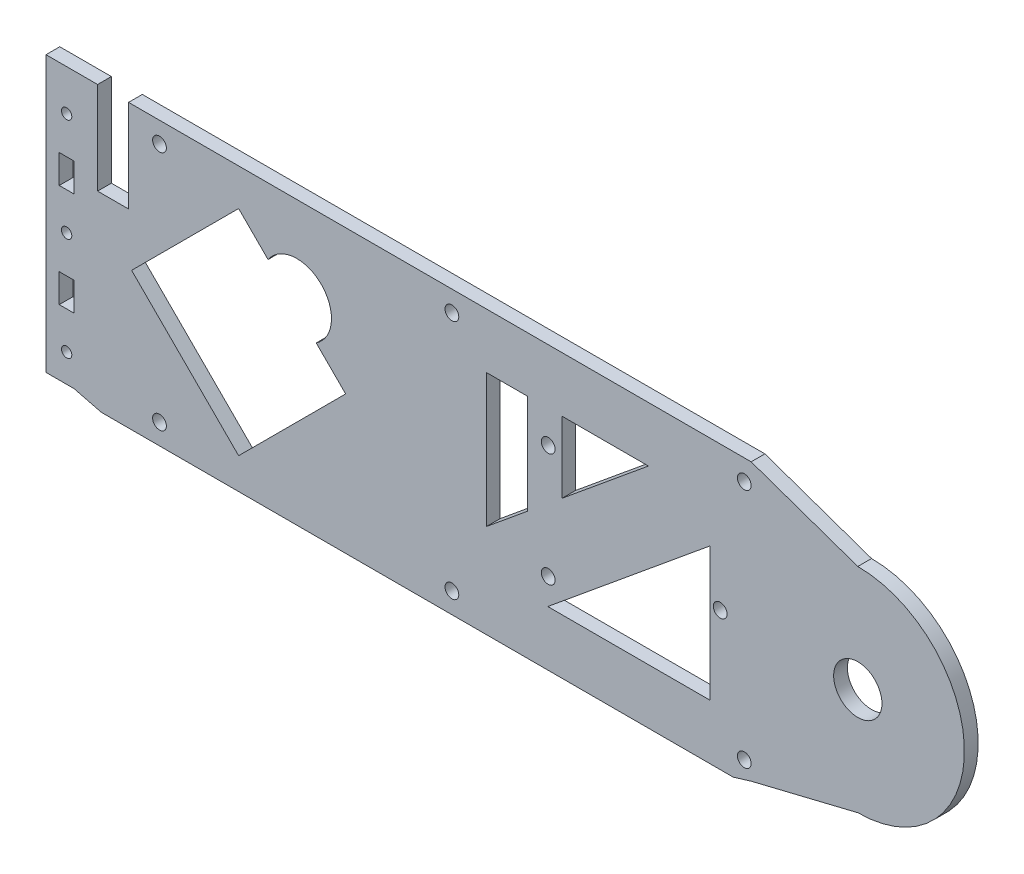
SolidWorks part; units mm, degrees
ref_plane "前视基准面" through (0, 0, 0) normal (0, 0, 1) x (1, 0, 0)
ref_plane "上视基准面" through (0, 0, 0) normal (0, 1, 0) x (1, 0, 0)
ref_plane "右视基准面" through (0, 0, 0) normal (1, 0, 0) x (0, 0, -1)
sketch "草图1" plane through (0, 0, 0) normal (0, 0, 1) x (1, 0, 0)
  line L0 (0.5429, 31.3543) -> (0.5429, 28.3543)
  line L1 (0.5429, 18.8543) -> (0.5429, 10.8543) construction
  line L2 (-1.6071, 10.7043) -> (2.6929, 10.7043)
  line L3 (-1.6071, 10.7043) -> (-1.6071, 19.0043)
  line L4 (-1.6071, 19.0043) -> (2.6929, 19.0043)
  line L5 (2.6929, 10.7043) -> (2.6929, 19.0043)
  line L6 (-1.6071, 10.7043) -> (2.6929, 19.0043) construction
  line L7 (-1.6071, 19.0043) -> (2.6929, 10.7043) construction
  line L8 (2.6929, -19.2957) -> (2.6929, -10.9957)
  line L9 (-1.6071, -19.2957) -> (2.6929, -19.2957)
  line L10 (-1.6071, -19.2957) -> (-1.6071, -10.9957)
  line L11 (-1.6071, -10.9957) -> (2.6929, -10.9957)
  line L12 (0.5429, -0.1457) -> (-6.4571, -0.1457) construction
  line L18 (50.5429, -0.1457) -> (96.7433, -0.1457) construction
  line L19 (50.5429, -0.1457) -> (230.5429, -0.1457) construction
  line L20 (199.5429, -0.1457) -> (199.5429, 38.0043) construction
  line L42 (230.5429, -31.1457) -> (199.5561, -38.7059)
  line L43 (199.5561, -38.7059) -> (174.5429, -46.2957)
  line L44 (174.5429, -46.2957) -> (34.5429, -46.2957)
  line L45 (34.5429, -46.2957) -> (2.6929, -38.2957)
  line L47 (2.6929, -38.2957) -> (-5.4571, -38.2957)
  line L48 (-5.4571, -38.2957) -> (-5.4571, 41.7043)
  line L49 (-5.4571, 41.7043) -> (9.5429, 41.7043)
  line L54 (199.5429, 41.7043) -> (230.5429, 30.8543)
  line L55 (9.5429, 41.7043) -> (9.5429, 14.8543)
  line L57 (9.5429, 14.8543) -> (18.5429, 14.8543)
  line L59 (-5.4571, 41.7043) -> (261.5429, 41.7043) construction
  line L60 (18.5429, 41.7043) -> (199.5429, 41.7043)
  line L61 (18.5429, 41.7043) -> (18.5429, 14.8543)
  line L62 (50.5429, 13.8543) -> (59.0992, 22.4106) construction
  line L63 (64.5429, -0.1457) -> (73.0992, 8.4106) construction
  line L64 (59.0992, 22.4106) -> (50.5429, 30.967)
  line L65 (19.4302, -0.1457) -> (50.5429, 30.967)
  line L66 (19.4302, -0.1457) -> (50.5429, -31.2584)
  line L67 (50.5429, -31.2584) -> (81.6556, -0.1457)
  line L68 (50.5429, 30.967) -> (81.6556, -0.1457) construction
  line L69 (19.4302, -0.1457) -> (81.6556, -0.1457) construction
  line L70 (50.5429, -31.2584) -> (50.5429, 30.967) construction
  line L71 (73.0992, 8.4106) -> (81.6556, -0.1457)
  line L72 (0.5429, -0.1457) -> (50.5429, -0.1457) construction
  circle A0 centre (0.5429, 29.8543) radius 1.5
  circle A1 centre (0.5429, -0.1457) radius 1.5
  circle A2 centre (0.5429, -30.1457) radius 1.5
  circle A15 centre (230.5429, -0.1457) radius 7.02
  circle A16 centre (230.5429, -0.1457) radius 31 construction
  arc A17 (230.5429, -31.1457) -> (230.5429, 30.8543) centre (230.5429, -0.1457) ccw
  circle A18 centre (50.5429, -0.1457) radius 34 construction
  arc A19 (59.0992, 22.4106) -> (73.0992, 8.4106) centre (67.4545, 16.7659) cw
  point P6 (0.5429, 14.8543)
  point P25 (50.5429, -0.1457)
  dimension "D3" = 44
  dimension "D4" = 44
  dimension "D10" = 3
  dimension "D13" = 14.04
  dimension "D1" = 8.3
  dimension "D2" = 4.3
  dimension "D5" = 50
  dimension "D7" = 15
  dimension "D8" = 60
  dimension "D9" = 30
  dimension "D14" = 180
extrude "凸台-拉伸1" add sketch "草图1" along normal blind 4 contours A2 A1 A0 L5 L2 L3 L4 L10 L11 L8 L9 region at (128.4702, -2.0106, 0)
sketch "草图3" plane through (0, 0, 4) normal (0, 0, 1) x (1, 0, 0)
  line L0 (18.5429, 41.7043) -> (199.5429, 41.7043) construction
  line L1 (18.5429, 41.7043) -> (18.5429, 14.8543) construction
  line L3 (112.5429, -34.2957) -> (197.5429, 35.7043) construction
  line L4 (197.5429, 35.7043) -> (197.5429, -34.2957) construction
  line L5 (197.5429, -34.2957) -> (112.5429, -34.2957) construction
  line L6 (187.5429, -24.2957) -> (140.4162, -24.2957)
  line L7 (140.4162, -24.2957) -> (187.5429, 14.5145)
  line L8 (187.5429, 14.5145) -> (187.5429, -24.2957)
  line L9 (112.5429, -34.2957) -> (112.5429, 35.7043) construction
  line L10 (112.5429, 35.7043) -> (197.5429, 35.7043) construction
  line L11 (122.5429, 25.7043) -> (169.6695, 25.7043)
  line L12 (122.5429, -13.1059) -> (169.6695, 25.7043)
  line L13 (122.5429, -13.1059) -> (122.5429, 25.7043)
  circle A0 centre (27.5429, 35.7043) radius 2
  circle A1 centre (112.5429, 35.7043) radius 2
  circle A2 centre (197.5429, 35.7043) radius 2
  circle A3 centre (112.5429, -34.2957) radius 2
  circle A4 centre (197.5429, -34.2957) radius 2
  circle A5 centre (27.5429, -34.2957) radius 2
  dimension "D1" = 6
  dimension "D2" = 9
  dimension "D5" = 10
  dimension "D6" = 10
  dimension "D3" = 3
  dimension "D4" = 2
extrude "切除-拉伸2" cut sketch "草图3" against normal blind 4
sketch "草图4" plane through (0, 0, 4) normal (0, 0, 1) x (1, 0, 0)
  line L0 (169.6695, 25.7043) -> (122.5429, 25.7043) construction
  line L1 (134.5429, -7.8425) -> (144.5429, -7.8425)
  line L2 (134.5429, -7.8425) -> (134.5429, 39.251)
  line L3 (134.5429, 39.251) -> (144.5429, 39.251)
  line L4 (144.5429, -7.8425) -> (144.5429, 39.251)
  line L5 (134.5429, -7.8425) -> (144.5429, 39.251) construction
  line L6 (134.5429, 39.251) -> (144.5429, -7.8425) construction
  point P0 (139.5429, 15.7043)
  dimension "D1" = 17
  dimension "D2" = 10
  dimension "D3" = 10
extrude "凸台-拉伸2" add sketch "草图4" against normal blind 4
sketch "草图7" plane through (0, 0, 4) normal (0, 0, 1) x (1, 0, 0)
  line L0 (10.6554, -40.2957) -> (194.3167, -40.2957)
  line L4 (34.5429, -46.2957) -> (2.6929, -38.2957) construction
  line L5 (199.5561, -38.7059) -> (174.5429, -46.2957) construction
  line L7 (10.6554, -40.2957) -> (10.6554, -65.8741)
  line L8 (10.6554, -65.8741) -> (206.1971, -67.6189)
  line L9 (206.1971, -67.6189) -> (194.3167, -40.2957)
  circle A0 centre (190.5429, -0.1457) radius 2
  circle A1 centre (140.5429, 16.3543) radius 2
  circle A2 centre (140.5429, -16.6457) radius 2
  point P12 (27.5429, -34.2957)
  point P25 (230.5429, -0.1457)
  dimension "D1" = 4
  dimension "D2" = 6
  dimension "D4" = 33
extrude "切除-拉伸3" cut sketch "草图7" against normal blind 4
